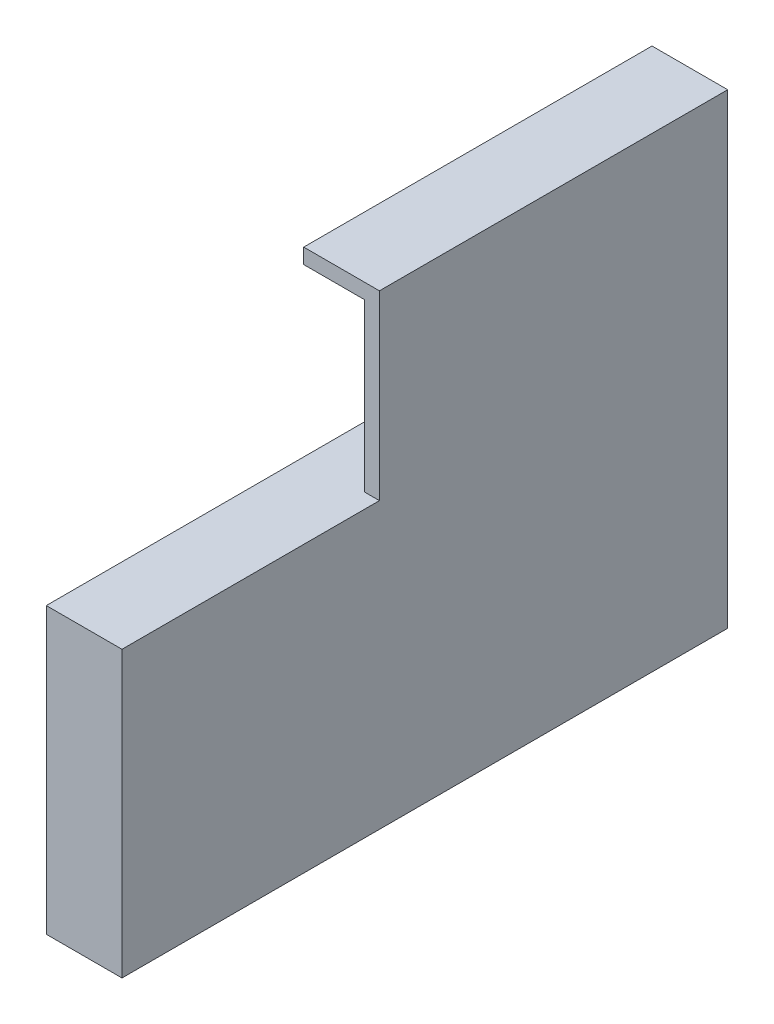
SolidWorks part; units mm, degrees
ref_plane "Front" through (0, 0, 0) normal (0, 0, 1) x (1, 0, 0)
ref_plane "Top" through (0, 0, 0) normal (0, 1, 0) x (1, 0, 0)
ref_plane "Right" through (0, 0, 0) normal (1, 0, 0) x (0, 0, -1)
sketch "Sketch1" plane through (0, 0, 0) normal (1, 0, 0) x (0, 0, -1)
  line L5 (0, 0) -> (95, 0)
  line L6 (0, 0) -> (0, 42)
  line L7 (0, 42) -> (95, 42)
  line L8 (95, 0) -> (95, 42)
  dimension "D1" = 95
  dimension "D2" = 42
extrude "Boss-Extrude2" add sketch "Sketch1" along normal blind 2.5
extrude "Extrude-Thin1" add sketch "Sketch1<2>" along normal blind 2.5 and the other way blind 10 thin thin type one direction wall 2.5
sketch "Sketch1<2>" plane through (0, 0, 0) normal (1, 0, 0) x (0, 0, -1) same geometry as "Sketch1"
sketch "Sketch2" plane through (2.5, 0, 0) normal (1, 0, 0) x (0, 0, -1)
  line L0 (97.5, 44.5) -> (97.5, 74.5)
  line L1 (97.5, 74.5) -> (37.5, 74.5)
  line L2 (37.5, 74.5) -> (37.5, 44.5)
  line L3 (97.5, 44.5) -> (-2.5, 44.5) construction
  line L4 (40, 44.5) -> (40, 72)
  line L5 (40, 72) -> (95, 72)
  line L6 (95, 72) -> (95, 44.5)
  line L7 (37.5, 44.5) -> (40, 44.5)
  line L8 (95, 44.5) -> (97.5, 44.5)
  line L9 (40, 44.5) -> (95, 44.5)
  line L10 (40, 72) -> (40, 74.5)
  line M10 (97.5, 44.5) -> (-2.5, 44.5)
  dimension "D1" = 30
  dimension "D2" = 60
  dimension "D3" = 2.5
  dimension "D4" = 2.5
  dimension "D5" = 2.5
extrude "Boss-Extrude3" add sketch "Sketch2" against normal blind 12.5 contours L5 L6 L0 L1 L2 L4 M10 region at (2.5, 45.1486, -96.25)
extrude "Boss-Extrude4" add sketch "Sketch2<4>" against normal blind 2.5 contours L6 L5 L4 M10 region at (2.5, 58.25, -67.5)
sketch "Sketch2<4>" plane through (2.5, 0, 0) normal (1, 0, 0) x (0, 0, -1) same geometry as "Sketch2"
